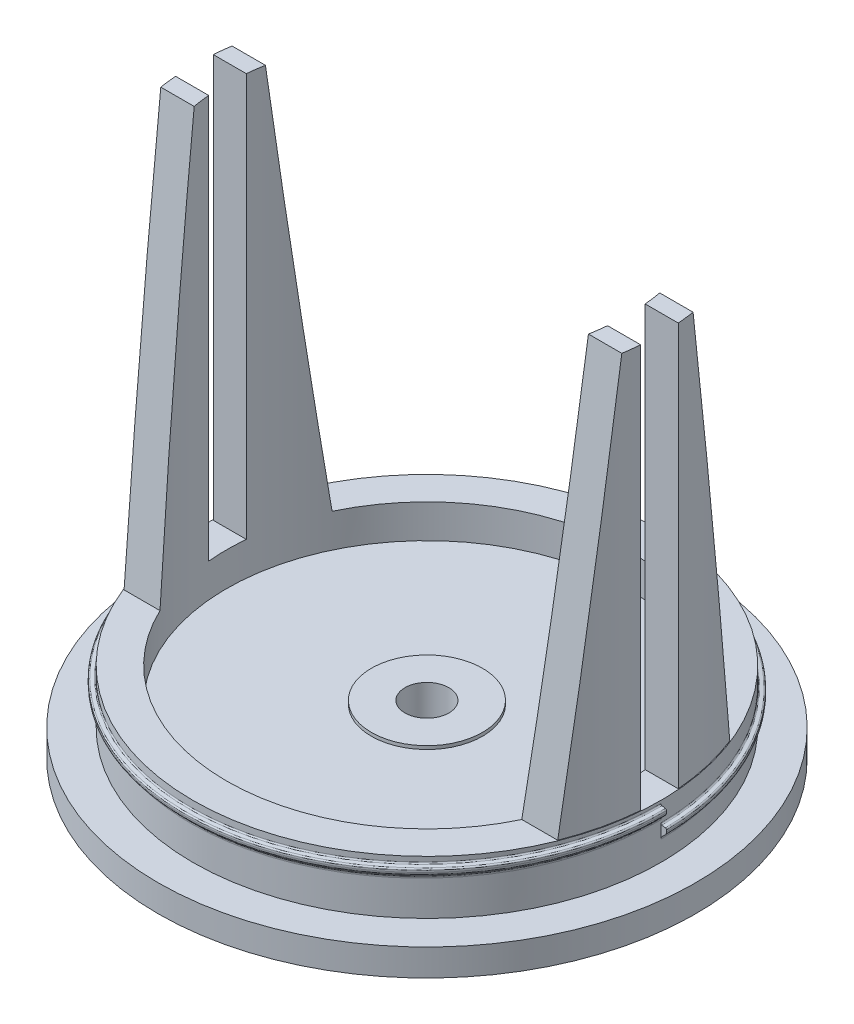
SolidWorks part; units mm, degrees
material "Nylon 101"
ref_plane "Front Plane" through (0, 0, 0) normal (0, 0, 1) x (1, 0, 0)
ref_plane "Top Plane" through (0, 0, 0) normal (0, 1, 0) x (1, 0, 0)
ref_plane "Right Plane" through (0, 0, 0) normal (1, 0, 0) x (0, 0, -1)
sketch "Sketch1" plane through (0, 0, 0) normal (0, 1, 0) x (1, 0, 0)
  circle A0 centre (0, 0) radius 50.8
  dimension "D1" = 101.6
extrude "Boss-Extrude1" add sketch "Sketch1" along normal blind 5.08
sketch "Sketch2" plane through (0, 5.08, 0) normal (0, 1, 0) x (1, 0, 0)
  circle A0 centre (0, 0) radius 44.196
  dimension "D1" = 88.392
extrude "Boss-Extrude2" add sketch "Sketch2" along normal blind 10.16
thread "Thread1" pitch 3.175 start angle 0, offset 3.81, length 3.175, pitch 3.175, diameter 88.392
ref_plane "Plane1" through (44.196, 8.89, 0) normal (0, 0, 1) x (1, 0, 0)
sketch "Thread Profile1" plane through (44.196, 8.89, 0) normal (0, 0, 1) x (1, 0, 0)
  line L0 (0, 0) -> (0, 3.175) construction
  line L1 (0, 0) -> (0, 2.6624)
  line L2 (0.254, 2.6624) -> (1.0668, 2.6624) construction
  line L3 (1.0668, 2.048) -> (1.0668, 1.6981)
  line L4 (0.8569, 2.2981) -> (0.2099, 2.4122)
  line L5 (0.8436, 1.1592) -> (0.2232, 0.5388)
  line L6 (0.762, 0) -> (1.0668, 0) construction
  arc A0 (0.2099, 2.4122) -> (0, 2.6624) centre (0.254, 2.6624) cw
  arc A1 (0.2232, 0.5388) -> (0, 0) centre (0.762, 0) ccw
  arc A2 (1.0668, 1.6981) -> (0.8436, 1.1592) centre (0.3048, 1.6981) cw
  arc A3 (1.0668, 2.048) -> (0.8569, 2.2981) centre (0.8128, 2.048) ccw
  point P10 (1.0668, 2.2611)
  point P17 (1.0668, 1.3824)
  point P18 (0, 2.4492)
  point P19 (0, 0.3156)
  point P20 (0, 0)
  dimension "RootFillet1" = 0.254
  dimension "RootFillet2" = 0.762
  dimension "CrestFillet2" = 0.762
  dimension "CrestFillet1" = 0.254
  dimension "Pitch" = 3.175
  dimension "Angle1" = 10
  dimension "Angle2" = 45
  dimension "a" = 2.1336
  dimension "b" = 1.0668
  dimension "c" = 0.8787
sketch "Sketch7" plane through (0, 0, 0) normal (0, -1, 0) x (1, 0, 0)
  circle A0 centre (0, 0) radius 4.15
  dimension "D1" = 8.3
extrude "Cut-Extrude1" cut sketch "Sketch7" against normal up to next
sketch "Sketch8" plane through (0, 15.24, 0) normal (0, 1, 0) x (1, 0, 0)
  circle A5 centre (0, 0) radius 37.846
  circle A7 centre (0, 0) radius 37.846
  circle A8 centre (0, 0) radius 10.5
  circle A9 centre (0, 0) radius 10.5
  dimension "D1" = 6.35
  dimension "D2" = 6.35
sketch "Sketch9" plane through (0, 0, 0) normal (0, -1, 0) x (1, 0, 0)
  line L0 (-44.45, 0) -> (-35.9, 0) construction
  line L5 (0, 50.8) -> (0, 0)
  line L6 (-44.3365, 3.175) -> (-35.7593, 3.175)
  line L7 (-44.3365, -3.175) -> (-35.7593, -3.175)
  line L8 (-50.8, 3.175) -> (50.8, 3.175) construction
  line L9 (-50.8, 0) -> (50.8, 0) construction
  line L10 (-50.8, -3.175) -> (50.8, -3.175) construction
  line L11 (35.7593, 3.175) -> (44.3365, 3.175)
  line L12 (0, 0) -> (44.45, 0) construction
  line L13 (35.7593, -3.175) -> (44.3365, -3.175)
  circle A1 centre (0, 0) radius 50.8 construction
  circle A4 centre (0, 0) radius 44.45
  circle A5 centre (0, 0) radius 44.45
  circle A7 centre (0, 0) radius 35.9
  circle A8 centre (0, 0) radius 35.9
  dimension "D1" = 6.35
  dimension "D2" = 31.75
  dimension "D3" = 3.175
  dimension "D4" = 3.175
extrude "Cut-Extrude4" cut sketch "Sketch8" against normal blind 6.35
sketch "Sketch10" plane through (0, 15.24, 0) normal (0, 1, 0) x (1, 0, 0)
  circle A1 centre (0, 0) radius 10.5
  circle A2 centre (0, 0) radius 10.5
  dimension "D1" = 0
extrude "Cut-Extrude5" cut sketch "Sketch10" against normal offset from surface (5.715 mm away) 9.525 up to face at (0, 0, -4.15)
sketch "Sketch11" plane through (0, 15.24, 0) normal (0, 1, 0) x (1, 0, 0)
  line L0 (-41.0978, 16.256) -> (-34.1769, 16.256)
  line L1 (-44.0527, 3.556) -> (-37.6786, 3.556)
  line L2 (-41.0978, -16.256) -> (-34.1769, -16.256)
  line L3 (-44.0527, -3.556) -> (-37.6786, -3.556)
  line L4 (-55.5308, 0) -> (55.5308, 0) construction
  circle A0 centre (0, 0) radius 37.846 construction
  circle A1 centre (0, 0) radius 44.196
  arc A2 (-41.0978, 16.256) -> (-44.0527, 3.556) centre (0, 0) ccw
  arc A3 (-34.1769, 16.256) -> (-37.6786, 3.556) centre (0, 0) ccw
  arc A4 (-37.6786, -3.556) -> (-34.1769, -16.256) centre (0, 0) ccw
  arc A5 (-44.0527, -3.556) -> (-41.0978, -16.256) centre (0, 0) ccw
  point P16 (-40.8656, 3.556)
  dimension "D2" = 3.556
  dimension "D3" = 3.556
  dimension "D4" = 12.7
  dimension "D5" = 12.7
extrude "Boss-Extrude3" add sketch "Sketch11" along normal blind 76.2
sketch "Sketch12" plane through (0, 0, 0) normal (1, 0, 0) x (0, 0, -1)
  line L0 (16.256, 91.44) -> (16.256, 15.24) construction
  line L1 (16.256, 91.44) -> (3.556, 91.44) construction
  line L2 (16.256, 91.44) -> (16.256, 15.24)
  line L3 (16.256, 91.44) -> (6.731, 91.44)
  line L4 (-16.256, 91.44) -> (-16.256, 15.24) construction
  line L5 (-3.556, 91.44) -> (-16.256, 91.44) construction
  line L6 (-16.256, 91.44) -> (-16.256, 15.24)
  line L7 (-6.731, 91.44) -> (-16.256, 91.44)
  line L8 (-16.256, 15.24) -> (-6.731, 91.44)
  line L9 (6.731, 91.44) -> (16.256, 15.24)
  dimension "D1" = 9.525
  dimension "D2" = 9.525
extrude "Cut-Extrude6" cut sketch "Sketch12" against normal up to next
pattern_circular "CirPattern2" count 2 over 360 about axis through (0, 15.241, 0) along (0, -1, 0) of "Boss-Extrude3", "Cut-Extrude6"
extrude "Cut-Extrude7" cut sketch "Sketch9" against normal blind 2.54 contours A8 L6 A5 L7 | A8 L13 A5 L11
fillet "Fillet1" radius 0.762 8 edges at (40.0479, 2.54, 3.175) (44.45, 2.54, 0) (40.0479, 2.54, -3.175) (35.9, 2.54, 0) (-40.0479, 2.54, -3.175) (-44.45, 2.54, 0) (-40.0479, 2.54, 3.175) (-35.9, 2.54, 0)
pattern_circular "CirPattern3" count 8 over 360 about axis through (0, 0, 0) along (0, 1, 0) of "Cut-Extrude7"
sketch "Sketch13" plane through (0, 0, 0) normal (0, -1, 0) x (1, 0, 0)
  line L0 (0, -55.5308) -> (0, 55.5308) construction
  line L1 (30.1625, -17.4143) -> (30.1625, 17.4143)
  line L2 (30.1625, 17.4143) -> (0, 34.8287)
  line L3 (0, 34.8287) -> (-30.1625, 17.4143)
  line L4 (-30.1625, 17.4143) -> (-30.1625, -17.4143)
  line L5 (-30.1625, -17.4143) -> (0, -34.8287)
  line L6 (0, -34.8287) -> (30.1625, -17.4143)
  circle A0 centre (0, 0) radius 30.1625 construction
  circle A1 centre (0, 0) radius 20.6375
  dimension "D2" = 9.525
  dimension "D1" = 60.325
extrude "Boss-Extrude4" add sketch "Sketch13" along normal blind 9.525
sketch "Sketch14" plane through (0, 15.24, 0) normal (0, 1, 0) x (1, 0, 0)
  circle A0 centre (0, 0) radius 44.069
  circle A1 centre (0, 0) radius 44.196
  dimension "D1" = 88.138
extrude "Cut-Extrude9" cut sketch "Sketch14" along normal up to next
equation "\"D3@Sketch11\"=\"D2@Sketch11\""
equation "\"D5@Sketch11\"=\"D4@Sketch11\""
equation "\"D2@Sketch12\"=\"D1@Sketch12\""
